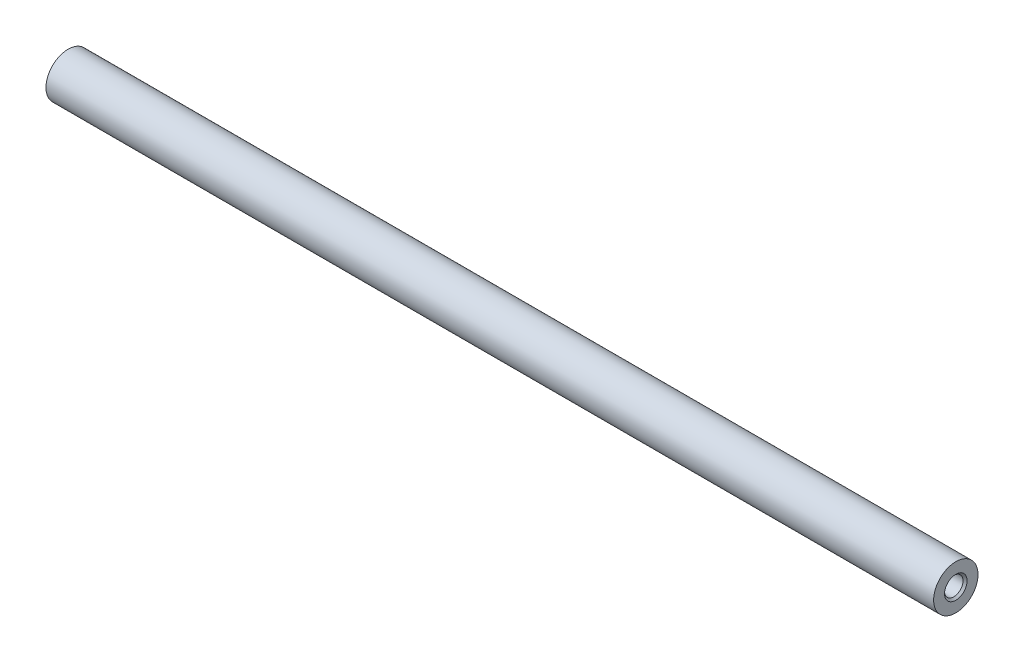
SolidWorks part; units mm, degrees
material "6061 合金"
ref_plane "前视基准面" through (0, 0, 0) normal (0, 0, 1) x (1, 0, 0)
ref_plane "上视基准面" through (0, 0, 0) normal (0, 1, 0) x (1, 0, 0)
ref_plane "右视基准面" through (0, 0, 0) normal (1, 0, 0) x (0, 0, -1)
sketch "草图1" plane through (0, 0, 0) normal (1, 0, 0) x (0, 0, -1)
  circle A0 centre (0, 0) radius 3
  dimension "D1" = 6
extrude "凸台-拉伸1" add sketch "草图1" along normal blind 120
hole_wizard "M3 螺纹孔1" positions "草图2" profile "草图3" tap size "M3" standard "GB" end condition through all
sketch "草图2" plane through (120, 0, 0) normal (1, 0, 0) x (0, 0, -1)
  point P0 (0, 0)
sketch "草图3" plane through (120, 0, 0) normal (0, 1, 0) x (0, 0, -1)
  line L0 (0, 0) -> (0, 120)
  line L1 (0, 120) -> (1.25, 120)
  line L2 (1.25, 120) -> (1.25, 0.275)
  line L3 (1.25, 0.275) -> (1.525, 0)
  line L5 (1.525, 0) -> (0, 0)
  line L6 (-1.25, 0.275) -> (-1.525, 0) construction
  line L11 (0, -6.35) -> (0, 107.95) construction
  dimension "通孔螺纹孔钻头直径" = 2.5
  dimension "通孔螺纹孔钻头深度" = 120
  dimension "近端锥形沉头孔直径" = 3.05
  dimension "近端锥形沉头孔角度" = 90
cosmetic thread "孔螺蚊线1"
